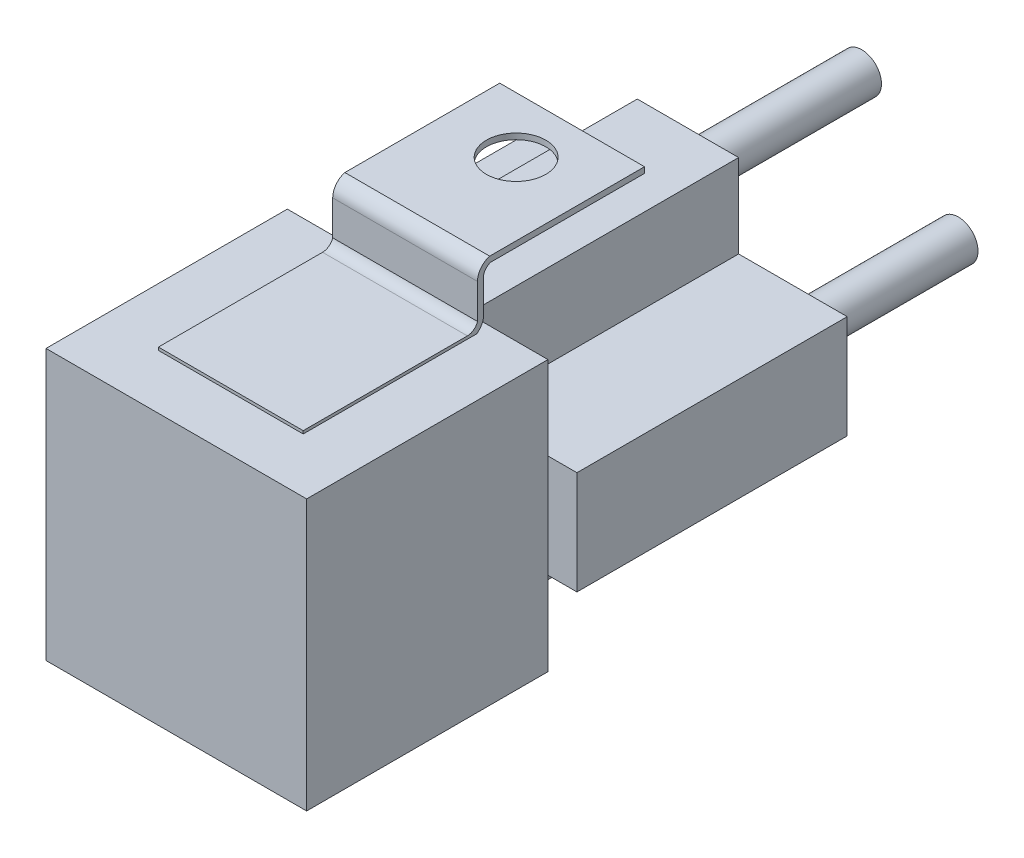
SolidWorks part; units mm, degrees
ref_plane "Front" through (0, 0, 0) normal (0, 0, 1) x (1, 0, 0)
ref_plane "Top" through (0, 0, 0) normal (0, 1, 0) x (1, 0, 0)
ref_plane "Right" through (0, 0, 0) normal (1, 0, 0) x (0, 0, -1)
sketch "Sketch1" plane through (0, 0, 0) normal (0, 0, 1) x (1, 0, 0)
  line L1 (-13.5, 14) -> (13.5, 14)
  line L2 (-13.5, 14) -> (-13.5, -14)
  line L3 (-13.5, -14) -> (13.5, -14)
  line L4 (13.5, 14) -> (13.5, -14)
  line L5 (-13.5, 14) -> (13.5, -14) construction
  line L6 (-13.5, -14) -> (13.5, 14) construction
  point P0 (0, 0)
  dimension "D1" = 27
  dimension "D2" = 28
extrude "Boss-Extrude1" add sketch "Sketch1" along normal blind 25
sketch "Sketch2" plane through (0, 0, 0) normal (0, 0, 1) x (1, 0, 0)
  line L0 (13.5, 14) -> (-13.5, 14) construction
  line L1 (-16.5, -5.35) -> (16.5, -5.35)
  line L2 (-16.5, -5.35) -> (-16.5, 5.35)
  line L3 (-16.5, 5.35) -> (16.5, 5.35)
  line L4 (16.5, -5.35) -> (16.5, 5.35)
  line L5 (-16.5, -5.35) -> (16.5, 5.35) construction
  line L6 (-16.5, 5.35) -> (16.5, -5.35) construction
  line L7 (-5.25, -14) -> (5.25, -14)
  line L8 (-5.25, -14) -> (-5.25, 14)
  line L9 (-5.25, 14) -> (5.25, 14)
  line L10 (5.25, -14) -> (5.25, 14)
  line L11 (-5.25, -14) -> (5.25, 14) construction
  line L12 (-5.25, 14) -> (5.25, -14) construction
  point P0 (0, 0)
  point P5 (0, 0)
  point P11 (-5.25, 14)
  dimension "D1" = 10.7
  dimension "D2" = 33
  dimension "D3" = 10.5
extrude "Boss-Extrude2" add sketch "Sketch2" against normal blind 28 contours L3 L4 L1 L2 | L8 L9 L10 L7
sketch "Sketch3" plane through (0, 0, -28) normal (0, 0, -1) x (-1, 0, 0)
  line L0 (0, 10) -> (0, 0) construction
  line L1 (0, 0) -> (0, -10) construction
  line L2 (-10, 0) -> (0, 0) construction
  line L3 (0, 0) -> (10, 0) construction
  circle A0 centre (-10, 0) radius 2.05
  circle A1 centre (10, 0) radius 2.05
  circle A2 centre (0, 10) radius 2.05
  circle A3 centre (0, -10) radius 2.05
  dimension "D1" = 4.1
  dimension "D2" = 10
extrude "Boss-Extrude3" add sketch "Sketch3" along normal blind 18
sketch "Sketch4" plane through (0, 0, 0) normal (1, 0, 0) x (0, 0, -1)
  line L0 (-19.3565, 14) -> (-2.3491, 14)
  line L1 (-25, 14) -> (0, 14) construction
  line L2 (-1, 15.0261) -> (-1, 18.6584)
  line L3 (0, 20) -> (16, 20)
  line L5 (28, 14) -> (0, 14) construction
  arc A0 (-2.3491, 14) -> (-1, 15.0261) centre (-2.3491, 15.4) ccw
  arc A1 (-1, 18.6584) -> (0, 20) centre (0.4, 18.6584) cw
  dimension "D1" = 6
  dimension "D4" = 1.4
  dimension "D2" = 16
  dimension "D3" = 1
extrude "Extrude-Thin1" add sketch "Sketch4" along normal mid plane 15 thin thin type mid plane wall 0.6
sketch "Sketch5" plane through (0, 20.3, 0) normal (0, 1, 0) x (1, 0, 0)
  circle A0 centre (0, 10.2) radius 3.075
  dimension "D1" = 6.15
  dimension "D2" = 10.2
extrude "Mounting Hole" cut sketch "Sketch5" against normal up to next
